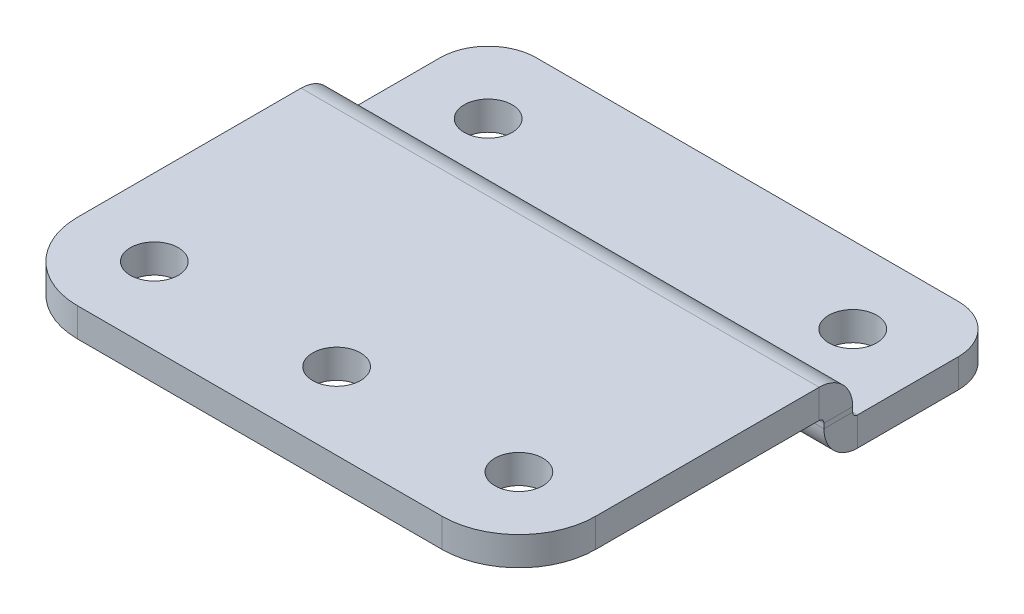
SolidWorks part; units mm, degrees
note: The reader was unsure of these and kept them because the rebuilt part matched: flange length of "Edge-Flange1", "Edge-Flange2".
ref_plane "Front Plane" through (0, 0, 0) normal (0, 0, 1) x (1, 0, 0)
ref_plane "Top Plane" through (0, 0, 0) normal (0, 1, 0) x (1, 0, 0)
ref_plane "Right Plane" through (0, 0, 0) normal (1, 0, 0) x (0, 0, -1)
sketch "Sketch1" plane through (0, 0, 0) normal (0, 1, 0) x (1, 0, 0)
  line L0 (27, 16) -> (27, 0) construction
  line L1 (0, 0) -> (54, 0)
  line L2 (0, 0) -> (0, 11)
  line L3 (5, 16) -> (49, 16)
  line L4 (54, 0) -> (54, 11)
  circle A0 centre (8, 8) radius 2.5
  circle A1 centre (46, 8) radius 2.5
  arc A2 (49, 16) -> (54, 11) centre (49, 11) cw
  arc A3 (0, 11) -> (5, 16) centre (5, 11) cw
  point P9 (27, 8)
  point P20 (0, 16)
  dimension "D3" = 19
  dimension "D4" = 5
  dimension "D5" = 5
  dimension "D1" = 16
  dimension "D2" = 54
  dimension "D6" = 8
base flange "Base-Flange1" sketch "Sketch1" thickness 3 reverse thickness direction no parameters "D1"=0.7366
edge flange "Edge-Flange1" sketch "Sketch8" flange angle 90 flange length 4 flange position material outside bend radius 0.5 thickness 3 relief rectangular parameters "D6"=10
sketch "Sketch8" plane through (0, 0, 0) normal (0, 0, 1) x (1, 0, 0)
  line L0 (0, 0) -> (54, 0) construction
  line L1 (0, 0) -> (54, 0)
  line L2 (0, 0) -> (0, 1)
  line L3 (0, 1) -> (54, 1)
  line L4 (54, 1) -> (54, 0)
bend "EdgeBend1" bend radius 0.5 bend angle 90 parameters "D5"=1
sketch "Sketch9" plane through (0, 1, 0) normal (0, 1, 0) x (1, 0, 0)
  line L0 (54, 0) -> (0, 0) construction
  line L1 (54, -3) -> (0, -3) construction
  line L2 (16, 0) -> (38, 0)
  line L3 (16, 0) -> (16, -3)
  line L4 (16, -3) -> (38, -3)
  line L5 (38, 0) -> (38, -3)
  line L6 (27, 0) -> (27, -3) construction
  point P10 (27, 0)
  dimension "D1" = 22
edge flange "Edge-Flange2" sketch "Sketch22" flange angle 90 flange length 34.8 flange position bend outside bend radius 0.5 thickness 3 relief rectangular parameters "D6"=10
sketch "Sketch22" plane through (0, 1, 3) normal (0, 1, 0) x (-1, 0, 0)
  line L2 (0, 0) -> (0, 31.8)
  line L3 (0, 31.8) -> (-54, 31.8)
  line L4 (-54, 31.8) -> (-54, 0)
  line L9 (-54, 0) -> (0, 0) construction
  line L10 (-54, 0) -> (0, 0)
bend "EdgeBend2" bend radius 0.5 bend angle 90 parameters "D5"=2
sketch "Sketch25" plane through (0, 4.5, 0) normal (0, 1, 0) x (1, 0, 0)
  line L0 (0, -34.8) -> (54, -34.8) construction
  line L1 (27, -34.8) -> (27, -3.5)
  line L2 (54, -34.8) -> (54, -3.5) construction
  line L3 (54, -26.8) -> (46, -26.8)
  line L4 (46, -34.8) -> (46, -26.8)
  line L7 (54, -26.8) -> (54, -34.8)
  line L8 (46, -34.8) -> (54, -34.8)
  line L9 (54, -3.5) -> (0, -3.5) construction
  line L12 (8, -34.8) -> (8, -26.8)
  line L13 (0, -26.8) -> (8, -26.8)
  line L14 (0, -26.8) -> (0, -34.8)
  line L15 (8, -34.8) -> (0, -34.8)
  line L16 (46, -26.8) -> (8, -26.8) construction
  circle A0 centre (46, -26.8) radius 8
  circle A2 centre (46, -26.8) radius 2.5
  circle A8 centre (8, -26.8) radius 2.5
  circle A9 centre (8, -26.8) radius 8
  circle A10 centre (27, -26.8) radius 2.5
  point P21 (27, -26.8)
  dimension "D2" = 8
  dimension "D4" = 8
extrude "Cut-Extrude1" cut sketch "Sketch25" against normal through all
sketch "Bend-Lines1" [suppressed] plane through (0, 0, 0) normal (0, 1, 0) x (1, 0, 0)
sketch "Bounding-Box1" [suppressed] plane through (0, 0, 0) normal (0, 1, 0) x (1, 0, 0)
sheet metal parameters "Sheet-Metal1" thickness 3 parameters "D1"=0.7366
flat pattern "Flat-Pattern1" [suppressed]
sketch "Bend-Lines2" plane through (0, 0, 0) normal (0, 1, 0) x (1, 0, 0)
sketch3d "Bounding-Box2" [suppressed]
  line L0 (6, 6, 0) -> (-48, 6, 0) construction
  line L1 (6, -10, 0) -> (-48, -10, 0) construction
  line L2 (6, 6, 0) -> (6, -10, 0) construction
  line L3 (-48, 6, 0) -> (-48, -10, 0) construction
sheet metal parameters "Sheet-Metal2" thickness 3 parameters "D1"=0.7366
flat pattern "Flat-Pattern1" [suppressed]
sketch "Bend-Lines2" plane through (0, 0, 0) normal (0, 1, 0) x (1, 0, 0)
  line L0 (0, -0.8352) -> (54, -0.8352) construction
  line L1 (0, -0.8352) -> (54, -0.8352) construction
sketch3d "Bounding-Box2" [suppressed]
  line L0 (-5, 5, 0) -> (49, 5, 0) construction
  line L1 (-5, -13.6704, 0) -> (49, -13.6703, 0) construction
  line L2 (-5, 5, 0) -> (-5, -13.6704, 0) construction
  line L3 (49, 5, 0) -> (49, -13.6703, 0) construction
bend of the flat pattern "Flatten-<EdgeBend1>1"
sketch "Sketch13-1" [suppressed] plane through (0, -3, 1.6704) normal (0, -1, 0) x (1, 0, 0)
  line L0 (16, 24) -> (38, 24)
  line L1 (8, 16) -> (46, 16) construction
  line L3 (16, 8) -> (38, 8)
  line L5 (16, 24) -> (16, 8)
  line L6 (38, 24) -> (38, 8)
  circle A0 centre (27, 16) radius 2.5
  dimension "D1" = 8
sketch "Sketch10-3" [suppressed] plane through (0, -3, 1.6704) normal (0, -1, 0) x (1, 0, 0)
  line L1 (54, 1) -> (0, 1) construction
  line L6 (54, 16) -> (54, 1)
  line L8 (38, 16) -> (0, 1)
  line L9 (16, 16) -> (54, 1)
  line L11 (0, 1) -> (0, 16)
  line L12 (8, 16) -> (46, 16) construction
  line L13 (0, 1) -> (54, 1)
  line L14 (16, 8) -> (38, 8)
  line L15 (54, 1) -> (0, 1)
  line L16 (16, 16) -> (16, 8)
  line L17 (38, 16) -> (38, 8)
  line L18 (0, 1) -> (8, 24)
  line L19 (46, 24) -> (54, 1)
  circle A0 centre (8, 16) radius 2.5
  circle A1 centre (46, 16) radius 2.5
  arc A2 (0, 16) -> (16, 16) centre (8, 16) cw
  arc A3 (38, 16) -> (54, 16) centre (46, 16) cw
  circle A4 centre (27, 16) radius 2.5
  dimension "D1" = 24.3516
  dimension "D2" = 5
  dimension "D3" = 5
  dimension "D5" = 8
  dimension "D6" = 8
  dimension "D4" = 15
  dimension "D7" = 8
sheet metal parameters "Sheet-Metal6" thickness 3 parameters "D1"=0.7366
flat pattern "Flat-Pattern1" [suppressed]
sketch "Bend-Lines2" plane through (0, 0, 0) normal (0, 1, 0) x (1, 0, 0)
  line L0 (0, -0.8352) -> (54, -0.8352) construction
  line L1 (0, -0.8352) -> (54, -0.8352) construction
  line L2 (0, -4.0055) -> (54, -4.0055) construction
  line L3 (0, -4.0055) -> (54, -4.0055) construction
sketch3d "Bounding-Box2" [suppressed]
  line L0 (-5, 5, 0) -> (49, 5, 0) construction
  line L1 (-5, -37.8407, 0) -> (49, -37.8407, 0) construction
  line L2 (-5, 5, 0) -> (-5, -37.8407, 0) construction
  line L3 (49, 5, 0) -> (49, -37.8407, 0) construction
bend of the flat pattern "Flatten-<EdgeBend1>1"
bend of the flat pattern "Flatten-<EdgeBend2>1"
sketch "Sketch13-1" [suppressed] plane through (0, -3, 1.6704) normal (0, -1, 0) x (1, 0, 0)
  line L0 (16, 24) -> (38, 24)
  line L1 (8, 16) -> (46, 16) construction
  line L3 (16, 8) -> (38, 8)
  line L5 (16, 24) -> (16, 8)
  line L6 (38, 24) -> (38, 8)
  circle A0 centre (27, 16) radius 2.5
  dimension "D1" = 8
sketch "Sketch10-3" [suppressed] plane through (0, -3, 1.6704) normal (0, -1, 0) x (1, 0, 0)
  line L1 (54, 1) -> (0, 1) construction
  line L6 (54, 16) -> (54, 1)
  line L8 (38, 16) -> (0, 1)
  line L9 (16, 16) -> (54, 1)
  line L11 (0, 1) -> (0, 16)
  line L12 (8, 16) -> (46, 16) construction
  line L13 (0, 1) -> (54, 1)
  line L14 (16, 8) -> (38, 8)
  line L15 (54, 1) -> (0, 1)
  line L16 (16, 16) -> (16, 8)
  line L17 (38, 16) -> (38, 8)
  line L18 (0, 1) -> (8, 24)
  line L19 (46, 24) -> (54, 1)
  circle A0 centre (8, 16) radius 2.5
  circle A1 centre (46, 16) radius 2.5
  arc A2 (0, 16) -> (16, 16) centre (8, 16) cw
  arc A3 (38, 16) -> (54, 16) centre (46, 16) cw
  circle A4 centre (27, 16) radius 2.5
  dimension "D1" = 24.3516
  dimension "D2" = 5
  dimension "D3" = 5
  dimension "D5" = 8
  dimension "D6" = 8
  dimension "D4" = 15
  dimension "D7" = 8
sheet metal parameters "Sheet-Metal7" thickness 3 parameters "D1"=0.7366
flat pattern "Flat-Pattern1"
sketch "Bend-Lines2" plane through (0, 1.5, 0) normal (0, -1, 0) x (-1, 0, 0)
  line L0 (-54, -2.1648) -> (0, -2.1648) construction
  line L1 (-54, 1.0055) -> (0, 1.0055) construction
  line L2 (-54, -2.1648) -> (0, -2.1648) construction
  line L3 (-54, 1.0055) -> (0, 1.0055) construction
sketch3d "Bounding-Box2" [suppressed]
  line L0 (0, 17.8407, 0) -> (-54, 17.8407, 0) construction
  line L1 (0, -34.8, 0) -> (-54, -34.8, 0) construction
  line L2 (0, 17.8407, 0) -> (0, -34.8, 0) construction
  line L3 (-54, 17.8407, 0) -> (-54, -34.8, 0) construction
bend of the flat pattern "Flatten-<EdgeBend2>1"
bend of the flat pattern "Flatten-<EdgeBend1>1"
